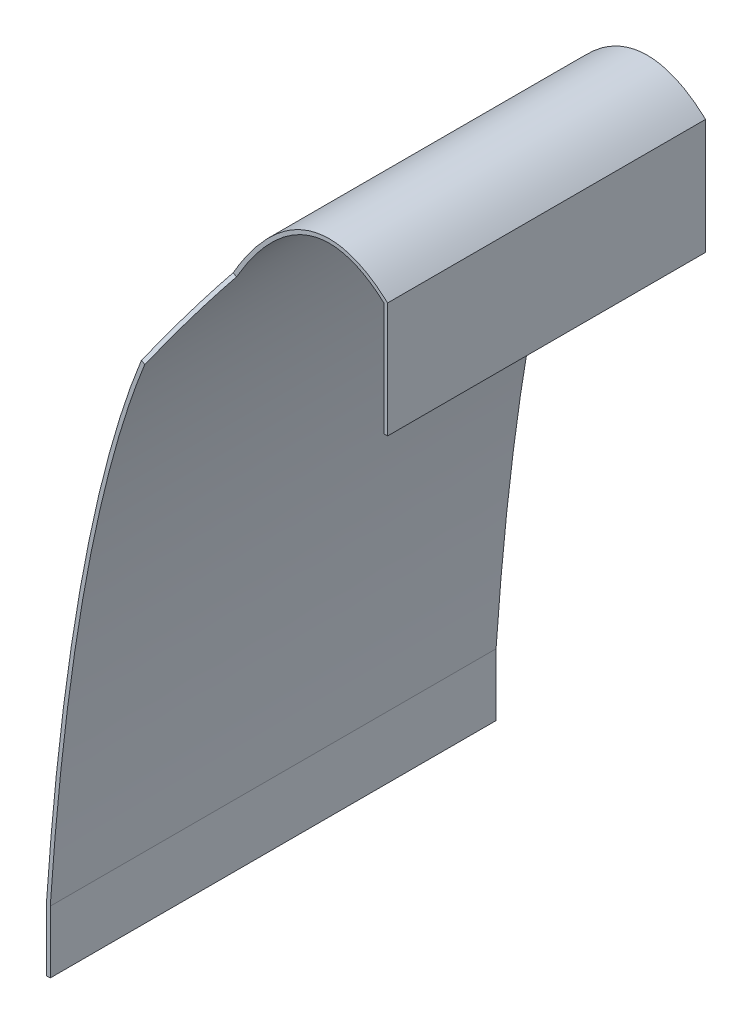
SolidWorks part; units mm, degrees
ref_plane "Front Plane" through (0, 0, 0) normal (0, 0, 1) x (1, 0, 0)
ref_plane "Top Plane" through (0, 0, 0) normal (0, 1, 0) x (1, 0, 0)
ref_plane "Right Plane" through (0, 0, 0) normal (1, 0, 0) x (0, 0, -1)
sketch "Sketch1" plane through (0, 0, 0) normal (0, 0, 1) x (1, 0, 0)
  line L0 (-1.4, 32.5) -> (0, 32.5) construction
  line L1 (-1.4, 32.5) -> (0, 32.5) construction
  line L2 (-13.4, 12.5) -> (-12.35, 12.5) construction
  line L3 (-13.4, 12.5) -> (-12.35, 12.5) construction
  line L4 (-1.725, 32) -> (-1.725, 36.15) construction
  line L5 (-1.4, 32) -> (-1.4, 32.5)
  line L6 (-1.4, 32.5) -> (-1.4, 33.4)
  line L7 (-1.4, 33.4) -> (-2.05, 33.4)
  line L8 (-2.05, 33.4) -> (-2.05, 32)
  line L9 (-2.05, 32) -> (-1.4, 32)
  line L10 (-1.4, 32) -> (-1.4, 32.5) construction
  line L11 (-1.4, 32.5) -> (-1.4, 33.4) construction
  line L12 (-1.4, 33.4) -> (-2.05, 33.4) construction
  line L13 (-2.05, 33.4) -> (-2.05, 32) construction
  line L14 (-2.05, 32) -> (-1.4, 32) construction
  line L15 (-11.65, 11.16) -> (-11.65, 13.42) construction
  line L16 (0, 32.5) -> (0, 38.12) construction
  line L17 (-12.17, 12.2) -> (-12.17, 11.17)
  line L18 (-12.17, 11.17) -> (-12.17, 11.16)
  line L19 (-12.17, 11.16) -> (-11.74, 11.16)
  line L20 (-11.74, 11.16) -> (-11.56, 11.16)
  line L21 (-11.56, 11.16) -> (-11.042, 11.16)
  line L22 (-11.042, 11.16) -> (-11.042, 12.07)
  line L23 (-10.912, 12.2) -> (-12.17, 12.2)
  line L24 (-12.17, 12.2) -> (-12.17, 11.17) construction
  line L25 (-12.17, 11.17) -> (-12.17, 11.16) construction
  line L26 (-12.17, 11.16) -> (-11.74, 11.16) construction
  line L27 (-11.74, 11.16) -> (-11.56, 11.16) construction
  line L28 (-11.56, 11.16) -> (-11.042, 11.16) construction
  line L29 (-11.042, 11.16) -> (-11.042, 12.07) construction
  line L30 (-10.912, 12.2) -> (-12.17, 12.2) construction
  line L31 (0, 38.12) -> (-13.4, 38.12) construction
  line L32 (-1.795, 32) -> (-1.795, 36.1189)
  line L33 (-11.58, 11.16) -> (-11.58, 13.4176)
  line L34 (-1.655, 32) -> (-1.655, 36.181)
  line L35 (-11.72, 11.16) -> (-11.72, 13.4224)
  line L36 (-11.72, 11.16) -> (-11.58, 11.16)
  line L37 (-1.795, 32) -> (-1.655, 32)
  arc A1 (-10.912, 12.2) -> (-11.042, 12.07) centre (-10.912, 12.07) ccw
  arc A2 (-10.912, 12.2) -> (-11.042, 12.07) centre (-10.912, 12.07) ccw construction
  spline S0 degree 3 poles (-1.725, 36.15) (-5.8402, 39.8806) (-10.3701, 32.2407) (-11.65, 13.42) knots 0 0 0 0 1 1 1 1 construction
  spline S1 degree 1 poles (-1.795, 36.1189) (-11.58, 13.4176) knots 0 0 1 1 construction
  spline S2 degree 3 poles (-1.795, 36.1189) (-1.9164, 36.2276) (-2.1778, 36.4392) (-2.6818, 36.757) (-3.3166, 36.9955) (-4.0694, 37.0212) (-5.0695, 36.7147) (-6.3084, 35.6763) (-7.7189, 33.367) (-9.0008, 30.0001) (-9.9244, 26.3167) (-10.5546, 22.8444) (-10.9674, 19.9795) (-11.2575, 17.3692) (-11.4536, 15.1607) (-11.5408, 13.9937) (-11.58, 13.4176) knots 0.001887 0.001887 0.001887 0.001887 0.033076 0.064266 0.126645 0.189025 0.251404 0.376163 0.500922 0.625681 0.75044 0.81282 0.875199 0.937579 0.968768 0.999958 0.999958 0.999958 0.999958
  spline S3 degree 1 poles (-1.655, 36.181) (-11.72, 13.4224) knots 0 0 1 1 construction
  spline S4 degree 3 poles (-1.655, 36.181) (-1.781, 36.2952) (-2.0493, 36.5197) (-2.575, 36.8612) (-3.2446, 37.1263) (-4.0503, 37.168) (-5.1135, 36.8576) (-6.3942, 35.7967) (-7.8269, 33.4687) (-9.1224, 30.084) (-10.0535, 26.3834) (-10.6884, 22.8949) (-11.104, 20.0164) (-11.3958, 17.3934) (-11.593, 15.1741) (-11.6806, 14.0013) (-11.72, 13.4224) knots -0.001862 -0.001862 -0.001862 -0.001862 0.029448 0.060757 0.123376 0.185995 0.248614 0.373852 0.49909 0.624328 0.749566 0.812185 0.874804 0.937423 0.968733 1.000042 1.000042 1.000042 1.000042
  dimension "D3" = 3.65
  dimension "D4" = 0.92
  dimension "D5" = 5.62
  dimension "D1" = 0
  dimension "D2" = 0
  dimension "D6" = 0.07
  dimension "D7" = 0.07
extrude "Boss-Extrude1" add sketch "Sketch1" along normal mid plane 11.54
sketch "Sketch2" plane through (0, 0, 5.77) normal (0, 0, 1) x (1, 0, 0)
  line L0 (-7.2617, 34.3266) -> (-7.1405, 34.2565)
  line L6 (-1.795, 32) -> (-1.655, 32)
  line L7 (-1.655, 32) -> (-1.655, 36.181)
  line L8 (-11.72, 13.4224) -> (-11.72, 11.16)
  line L9 (-11.72, 11.16) -> (-11.58, 11.16)
  line L10 (-11.58, 11.16) -> (-11.58, 13.4176)
  line L11 (-1.795, 36.1189) -> (-1.795, 32)
  line L14 (-11.72, 13.4224) -> (-11.72, 11.16)
  line L15 (-11.72, 11.16) -> (-11.58, 11.16)
  line L16 (-11.58, 11.16) -> (-11.58, 13.4176)
  spline S2 degree 3 poles (-1973.057, 2297.1894) (18.5538, -22.8222) (5.639, 31.5262) (-2.575, 36.8612) (-3.2446, 37.1263) (-4.0503, 37.168) (-5.1135, 36.8576) (-6.3942, 35.7967) (-7.8269, 33.4687) (-9.1224, 30.084) (-10.0535, 26.3834) (-10.6884, 22.8949) (-11.104, 20.0164) (-11.3958, 17.3934) (-14.0892, -12.9183) (-9.0582, -85.8555) (233.2444, 3003.2687) knots -1.833332 -1.833332 -1.833332 -1.833332 0.029448 0.060757 0.123376 0.185995 0.248614 0.373852 0.49909 0.624328 0.749566 0.812185 0.874804 0.937423 0.968733 2.585317 2.585317 2.585317 2.585317 only from (-1.655, 36.181) to (-11.72, 13.4224)
  spline S3 degree 3 poles (236.4054, 3003.0309) (-8.9595, -85.6029) (-13.9414, -12.8525) (-11.2575, 17.3692) (-10.9674, 19.9795) (-10.5546, 22.8444) (-9.9244, 26.3167) (-9.0008, 30.0001) (-7.7189, 33.367) (-6.3084, 35.6763) (-5.0695, 36.7147) (-4.0694, 37.0212) (-3.3166, 36.9955) (-2.6818, 36.757) (5.092, 31.8556) (20.9836, -19.8679) (-2308.245, 1954.1995) knots -1.580599 -1.580599 -1.580599 -1.580599 0.033076 0.064266 0.126645 0.189025 0.251404 0.376163 0.500922 0.625681 0.75044 0.81282 0.875199 0.937579 0.968768 2.799463 2.799463 2.799463 2.799463 only from (-11.58, 13.4176) to (-1.795, 36.1189)
  spline S4 degree 3 poles (-7.2617, 34.3266) (-7.4457, 34.0088) (-8.0903, 32.7807) (-9.1224, 30.084) (-10.0535, 26.3834) (-10.6884, 22.8949) (-11.104, 20.0164) (-11.3958, 17.3934) (-11.593, 15.1741) (-11.6806, 14.0013) (-11.72, 13.4224) knots 0.450226 0.450226 0.450226 0.450226 0.49909 0.624328 0.749566 0.812185 0.874804 0.937423 0.968733 1.000042 1.000042 1.000042 1.000042
  spline S5 degree 3 poles (-11.58, 13.4176) (-11.5408, 13.9937) (-11.4536, 15.1607) (-11.2575, 17.3692) (-10.9674, 19.9795) (-10.5546, 22.8444) (-9.9244, 26.3167) (-9.0008, 30.0001) (-7.9726, 32.7007) (-7.3293, 33.9303) (-7.1405, 34.2565) knots 0.001887 0.001887 0.001887 0.001887 0.033076 0.064266 0.126645 0.189025 0.251404 0.376163 0.500922 0.551612 0.551612 0.551612 0.551612
  dimension "D1" = 0
extrude "Boss-Extrude2" add sketch "Sketch2" along normal up to surface (2.32 mm away)
sketch "Sketch3" plane through (0, 0, -5.77) normal (0, 0, -1) x (-1, 0, 0)
  line L4 (11.72, 11.16) -> (11.72, 13.4224)
  line L5 (11.58, 11.16) -> (11.72, 11.16)
  line L6 (11.58, 13.4176) -> (11.58, 11.16)
  line L7 (7.2617, 34.3266) -> (7.1405, 34.2565)
  line L8 (11.72, 11.16) -> (11.72, 13.4224)
  line L9 (11.58, 11.16) -> (11.72, 11.16)
  line L10 (11.58, 13.4176) -> (11.58, 11.16)
  line L11 (7.2617, 34.3266) -> (7.1405, 34.2565)
  spline S2 degree 3 poles (1953.7281, -2197.0578) (-137.4038, -566.5988) (-19.1791, 104.0135) (9.0008, 30.0001) (9.9244, 26.3167) (10.5546, 22.8444) (10.9674, 19.9795) (11.2575, 17.3692) (13.9413, -12.8516) (8.9599, -85.5983) (-236.3816, 3002.7313) knots -7.925595 -7.925595 -7.925595 -7.925595 0.052576 0.177335 0.302094 0.364473 0.426853 0.489232 0.520422 2.134046 2.134046 2.134046 2.134046 only from (7.1405, 34.2565) to (11.58, 13.4176)
  spline S3 degree 3 poles (-233.2404, 3003.2175) (9.0583, -85.8547) (14.0892, -12.9181) (11.3958, 17.3934) (11.104, 20.0164) (10.6884, 22.8949) (10.0535, 26.3834) (9.1224, 30.084) (-23.0059, 114.0272) (-177.9457, -752.0781) (1645.9046, -2412.6199) knots -1.13504 -1.13504 -1.13504 -1.13504 0.481536 0.512845 0.575464 0.638083 0.700702 0.82594 0.951178 10.018511 10.018511 10.018511 10.018511 only from (11.72, 13.4224) to (7.2617, 34.3266)
  spline S4 degree 3 poles (7.1405, 34.2565) (7.3293, 33.9303) (7.9726, 32.7007) (9.0008, 30.0001) (9.9244, 26.3167) (10.5546, 22.8444) (10.9674, 19.9795) (11.2575, 17.3692) (11.4536, 15.1607) (11.5408, 13.9937) (11.58, 13.4176) knots 0.001887 0.001887 0.001887 0.001887 0.052576 0.177335 0.302094 0.364473 0.426853 0.489232 0.520422 0.551612 0.551612 0.551612 0.551612
  spline S5 degree 3 poles (11.72, 13.4224) (11.6806, 14.0013) (11.593, 15.1741) (11.3958, 17.3934) (11.104, 20.0164) (10.6884, 22.8949) (10.0535, 26.3834) (9.1224, 30.084) (8.0903, 32.7807) (7.4457, 34.0088) (7.2617, 34.3266) knots 0.450226 0.450226 0.450226 0.450226 0.481536 0.512845 0.575464 0.638083 0.700702 0.82594 0.951178 1.000042 1.000042 1.000042 1.000042
  dimension "D1" = 0
extrude "Boss-Extrude3" add sketch "Sketch3" along normal up to surface (2.32 mm away)
chamfer "Chamfer1" distance 2.32 angle 45 2 edges at (-7.2011, 34.2916, -8.09) (-7.2011, 34.2916, 8.09)
